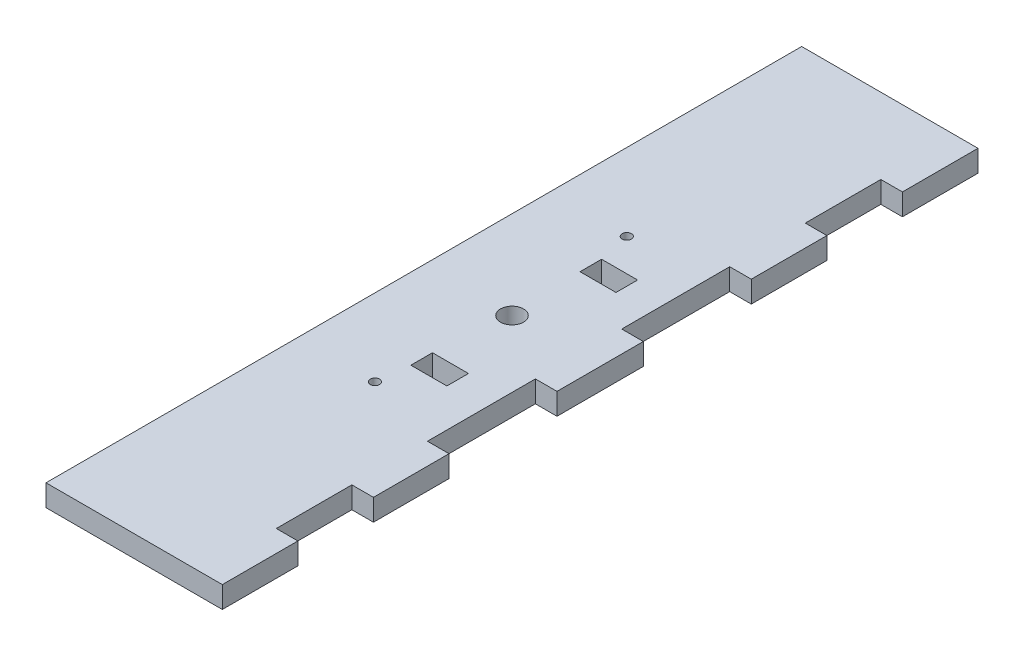
SolidWorks part; units mm, degrees
material "Balsa"
ref_plane "Front Plane" through (0, 0, 0) normal (0, 0, 1) x (1, 0, 0)
ref_plane "Top Plane" through (0, 0, 0) normal (0, 1, 0) x (1, 0, 0)
ref_plane "Right Plane" through (0, 0, 0) normal (1, 0, 0) x (0, 0, -1)
sketch "Sketch1" plane through (0, 0, 0) normal (0, 1, 0) x (1, 0, 0)
  line L0 (0, 0) -> (0, 105) construction
  line L1 (-24.5, 105) -> (24.5, 105)
  line L2 (-24.5, 105) -> (-24.5, -105)
  line L3 (-24.5, -105) -> (24.5, -105)
  line L4 (24.5, 105) -> (24.5, -105)
  line L5 (0, 0) -> (24.5, 0) construction
  circle A0 centre (0, 0) radius 3.2
  dimension "D3" = 6.4
  dimension "D1" = 210
  dimension "D2" = 49
extrude "Boss-Extrude1" add sketch "Sketch1" along normal blind 6
sketch "Sketch2" plane through (0, 6, 0) normal (0, 1, 0) x (1, 0, 0)
  line L1 (24.5, -105) -> (24.5, 105) construction
  line L2 (18.5, 84) -> (24.5, 84)
  line L3 (18.5, 84) -> (18.5, 63)
  line L4 (18.5, 63) -> (24.5, 63)
  line L5 (24.5, 84) -> (24.5, 63)
  line L6 (0, 0) -> (24.5, 0) construction
  line L7 (18.5, 42) -> (24.5, 42)
  line L8 (18.5, 42) -> (18.5, 12)
  line L9 (18.5, 12) -> (24.5, 12)
  line L10 (24.5, 42) -> (24.5, 12)
  line L12 (24.5, 105) -> (-24.5, 105) construction
  line L13 (24.5, -42) -> (24.5, -12)
  line L14 (18.5, -12) -> (24.5, -12)
  line L15 (18.5, -42) -> (18.5, -12)
  line L16 (18.5, -42) -> (24.5, -42)
  line L17 (24.5, -84) -> (24.5, -63)
  line L18 (18.5, -63) -> (24.5, -63)
  line L19 (18.5, -84) -> (18.5, -63)
  line L20 (18.5, -84) -> (24.5, -84)
  dimension "D1" = 21
  dimension "D2" = 30
  dimension "D3" = 21
  dimension "D4" = 21
  dimension "D5" = 6
extrude "Cut-Extrude1" cut sketch "Sketch2" against normal through all
sketch "Sketch3" plane through (0, 6, 0) normal (0, 1, 0) x (1, 0, 0)
  line L1 (-2.1, -26) -> (7.9, -26)
  line L2 (-2.1, -26) -> (-2.1, -20)
  line L3 (-2.1, -20) -> (7.9, -20)
  line L4 (7.9, -26) -> (7.9, -20)
  line L5 (-1.1, 20) -> (8.9, 20)
  line L6 (-1.1, 20) -> (-1.1, 26)
  line L7 (-1.1, 26) -> (8.9, 26)
  line L8 (8.9, 20) -> (8.9, 26)
extrude "Cut-Extrude2" cut sketch "Sketch3" against normal through all
sketch "Sketch4" plane through (0, 6, 0) normal (0, 1, 0) x (1, 0, 0)
  line L0 (24.5, 0) -> (-24.5, 0) construction
  line L1 (24.5, -12) -> (24.5, 12) construction
  line L2 (-24.5, 105) -> (-24.5, -105) construction
  circle A0 centre (-3.1, -35) radius 1.3
  circle A1 centre (-3.1, 35) radius 1.3
  dimension "D1" = 2.6
extrude "Cut-Extrude3" cut sketch "Sketch4" against normal through all
